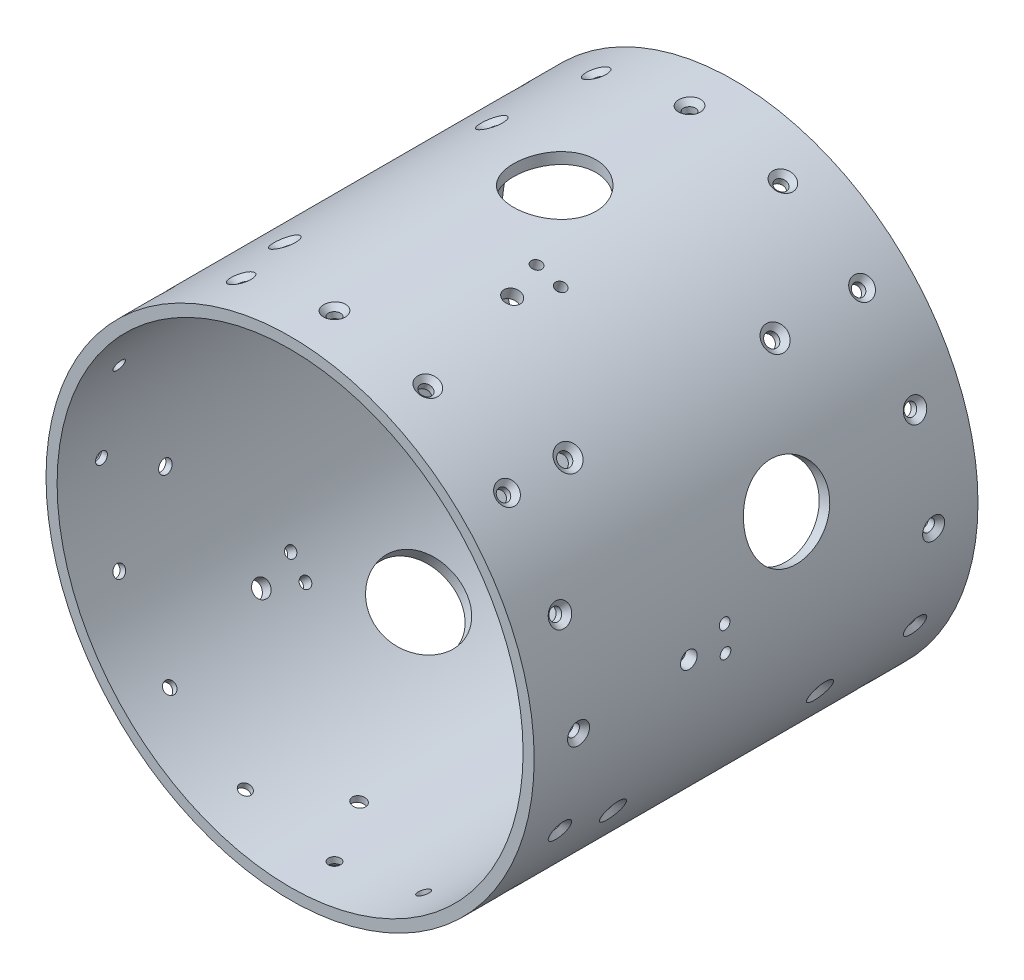
SolidWorks part; units mm, degrees
ref_plane "Front Plane" through (0, 0, 0) normal (0, 0, 1) x (1, 0, 0)
ref_plane "Top Plane" through (0, 0, 0) normal (0, 1, 0) x (1, 0, 0)
ref_plane "Right Plane" through (0, 0, 0) normal (1, 0, 0) x (0, 0, -1)
sketch "Sketch1" plane through (0, 0, 0) normal (0, 0, 1) x (1, 0, 0)
  circle A0 centre (0, 0) radius 66.675
  circle A1 centre (0, 0) radius 69.85
  dimension "D1" = 133.35
  dimension "D2" = 139.7
extrude "Extrude1" add sketch "Sketch1" along normal blind 63.5
ref_plane "Plane2" through (0, 0, 50.8) normal (0, 0, 1) x (1, 0, 0)
sketch "Sketch2" plane through (0, 0, 50.8) normal (0, 0, 1) x (1, 0, 0)
  circle A0 centre (0, 0) radius 69.85 construction
  point P0 (0, -69.85)
ref_plane "Plane3" through (0, -69.85, 50.8) normal (0, -1, 0) x (1, 0, 0)
hole_wizard "CSK for M3 Flat Head Machine Screw1" positions "Sketch4" profile "Sketch3" countersink size "M3" standard "Ansi Metric" end condition through all
sketch "Sketch4" plane through (0, -69.85, 50.8) normal (0, -1, 0) x (1, 0, 0)
  point P1 (0, 0)
sketch "Sketch3" plane through (0, -69.85, 50.8) normal (1, 0, 0) x (0, 0, -1)
  line L0 (0, 0) -> (0, 161.1134)
  line L1 (0, 161.1134) -> (1.7, 161.1134)
  line L2 (1.7, 161.1134) -> (1.7, 1.45)
  line L3 (1.7, 1.45) -> (3.15, 0)
  line L5 (3.15, 0) -> (0, 0)
  line L6 (-1.7, 1.45) -> (-3.15, 0) construction
  line L11 (0, -6.35) -> (0, 107.95) construction
  dimension "Thru Hole Dia." = 3.4
  dimension "Thru Hole Depth" = 161.1134
  dimension "Near C'Sink Dia." = 6.3
  dimension "Near C'Sink Angle" = 90
pattern_circular "CirPattern1" count 16 over 360 about axis through (0, 0, 63.5) along (0, 0, -1) of "CSK for M3 Flat Head Machine Screw1"
mirror "Mirror1" about plane through (0, 0, 0) normal (0, 0, 1) of "CSK for M3 Flat Head Machine Screw1", "CirPattern1", "Extrude1"
sketch "Sketch6" plane through (0, -69.85, 50.8) normal (0, -1, 0) x (1, 0, 0)
  line L0 (0, 12.7) -> (0, -139.319) construction
  line L1 (66.675, 12.7) -> (-66.675, 12.7) construction
  line L2 (0, 12.7) -> (0, -114.3) construction
  line L3 (0, 12.7) -> (0, -37.719) construction
  line L4 (0, 12.7) -> (0, -393.319) construction
  dimension "D1" = 101.6
  dimension "D2" = 50.419
  dimension "D3" = 355.6
ref_plane "Plane4" through (0, 0, 0) normal (-0.7071, -0.7071, 0) x (0.7071, -0.7071, 0)
sketch "Sketch15" plane through (0, 0, -63.5) normal (0, 0, -1) x (-1, 0, 0)
  line L0 (0, 0) -> (0, 69.85) construction
  line L1 (0, 69.85) -> (0, 0) construction
  line L2 (0, 0) -> (-15.7722, 68.046) construction
  line L3 (0, 0) -> (-19.2571, 67.143) construction
  line L4 (0, 0) -> (-22.6931, 66.0609) construction
  line L5 (0, 0) -> (-49.3914, 49.3914) construction
  circle A0 centre (0, 0) radius 69.85 construction
  dimension "D1" = 0
  dimension "D2" = 3.6
  dimension "D3" = 15.875
  dimension "D4" = 7.2
  dimension "D5" = 45
  dimension "D6" = 13.05
  dimension "D7" = 2.953
  dimension "D8" = 2.955
  dimension "D9" = 18.959
  dimension "D10" = 16.003
ref_plane "Plane6" through (0, 69.85, -63.5) normal (0, 1, 0) x (-1, 0, 0)
ref_plane "Plane7" through (19.2571, 67.143, -63.5) normal (0.2757, 0.9612, 0) x (0, 0, 1)
ref_plane "Plane8" through (15.7722, 68.046, -63.5) normal (0.2258, 0.9742, 0) x (-0.9742, 0.2258, 0)
ref_plane "Plane9" through (22.6931, 66.0609, -63.5) normal (0.3249, 0.9458, 0) x (-0.9458, 0.3249, 0)
sketch "Sketch16" plane through (0, 69.85, -63.5) normal (0, 1, 0) x (-1, 0, 0)
  line L0 (0, 51.2766) -> (0, 0) construction
  line L1 (69.85, 127) -> (-69.85, 127) construction
  line L2 (-69.85, 0) -> (69.85, 0) construction
  circle A0 centre (0, 51.2766) radius 11.8
  dimension "D1" = 23.6
  dimension "D2" = 75.7234
  dimension "D3" = 51.2766
extrude "Cut-Extrude1" cut sketch "Sketch16" against normal blind 7.62
sketch "Sketch17" plane through (19.2571, 67.143, -63.5) normal (0.2757, 0.9612, 0) x (0, 0, 1)
  line L0 (0, 0) -> (82.6966, 0) construction
  dimension "D1" = 31.42
sketch "Sketch18" plane through (15.7722, 68.046, -63.5) normal (0.2258, 0.9742, 0) x (-0.9742, 0.2258, 0)
  line L0 (0, 0) -> (0, 72.2466) construction
  dimension "D1" = 10.45
  dimension "D2" = 72.2466
sketch "Sketch27" plane through (22.6931, 66.0609, -63.5) normal (0.3249, 0.9458, 0) x (-0.9458, 0.3249, 0)
  line L0 (0, 0) -> (0, 72.2466) construction
  line L1 (7.1904, 0) -> (7.1904, 72.2466) construction
hole_wizard "#31 (0.12) Diameter Hole1" positions "Sketch22" profile "Sketch23" hole size "#31" standard "ANSI Inch"
sketch "Sketch22" plane through (15.7722, 68.046, -63.5) normal (0.2258, 0.9742, 0) x (-0.9742, 0.2258, 0)
  point P1 (0, 72.2466)
sketch "Sketch23" plane through (15.7722, 68.046, 8.7466) normal (0, 0, 1) x (-0.9742, 0.2258, 0)
  line L0 (0, 0) -> (0, 12.5997)
  line L1 (0, 12.5997) -> (1.524, 11.684)
  line L2 (1.524, 11.684) -> (1.524, 0)
  line L5 (1.524, 0) -> (0, 0)
  line L10 (0, 12.5997) -> (-1.524, 11.684) construction
  line L11 (0, -6.35) -> (0, 107.95) construction
  dimension "Hole Dia." = 3.048
  dimension "Hole Depth" = 11.684
  dimension "Drill Angle" = 118
hole_wizard "3/16 (0.1875) Diameter Hole1" positions "Sketch25" profile "Sketch26" hole size "3/16" standard "ANSI Inch"
sketch "Sketch25" plane through (19.2571, 67.143, -63.5) normal (0.2757, 0.9612, 0) x (0, 0, 1)
  point P1 (82.6966, 0)
sketch "Sketch26" plane through (19.2571, 67.143, 19.1966) normal (0, 0, 1) x (-0.9612, 0.2757, 0)
  line L0 (0, 0) -> (0, 13.1148)
  line L1 (0, 13.1148) -> (2.3812, 11.684)
  line L2 (2.3812, 11.684) -> (2.3812, 0)
  line L5 (2.3812, 0) -> (0, 0)
  line L10 (0, 13.1148) -> (-2.3813, 11.684) construction
  line L11 (0, -6.35) -> (0, 107.95) construction
  dimension "Hole Dia." = 4.7625
  dimension "Hole Depth" = 11.684
  dimension "Drill Angle" = 118
hole_wizard "#31 (0.12) Diameter Hole3" positions "Sketch29" profile "Sketch28" hole size "#31" standard "ANSI Inch"
sketch "Sketch29" plane through (22.6931, 66.0609, -63.5) normal (0.3249, 0.9458, 0) x (-0.9458, 0.3249, 0)
  point P0 (0, 72.2466)
sketch "Sketch28" plane through (22.6931, 66.0609, 8.7466) normal (0, 0, 1) x (-0.9458, 0.3249, 0)
  line L0 (0, 0) -> (0, 12.5997)
  line L1 (0, 12.5997) -> (1.524, 11.684)
  line L2 (1.524, 11.684) -> (1.524, 0)
  line L5 (1.524, 0) -> (0, 0)
  line L10 (0, 12.5997) -> (-1.524, 11.684) construction
  line L11 (0, -6.35) -> (0, 107.95) construction
  dimension "Hole Dia." = 3.048
  dimension "Hole Depth" = 11.684
  dimension "Drill Angle" = 118
ref_plane "Plane10" through (49.3914, 49.3914, -63.5) normal (0.7071, 0.7071, 0) x (-0.7071, 0.7071, 0)
sketch "Sketch30" plane through (49.3914, 49.3914, -63.5) normal (0.7071, 0.7071, 0) x (-0.7071, 0.7071, 0)
  line L0 (0, 0) -> (0, 37.5945) construction
  line L1 (0, 37.5945) -> (0, 96.8375) construction
  line L3 (66.675, 127) -> (-66.675, 127) construction
  dimension "D1" = 30.1625
  dimension "D2" = 59.243
  dimension "D3" = 37.5945
  dimension "D4" = 96.8375
hole_wizard "CSK for #6 Flat Head Machine Screw (100)1" positions "Sketch34" profile "Sketch35" countersink size "#6" standard "ANSI Inch"
sketch "Sketch34" plane through (49.3914, 49.3914, -63.5) normal (0.7071, 0.7071, 0) x (-0.7071, 0.7071, 0)
  point P0 (0, 96.8375)
  point P3 (0, 37.5945)
sketch "Sketch35" plane through (49.3914, 49.3914, 33.3375) normal (0, 0, 1) x (-0.7071, 0.7071, 0)
  line L0 (0, 0) -> (0, 16.3808)
  line L1 (0, 16.3808) -> (1.8986, 15.24)
  line L2 (1.8986, 15.24) -> (1.8986, 1.38)
  line L3 (1.8986, 1.38) -> (3.5433, 0)
  line L5 (3.5433, 0) -> (0, 0)
  line L6 (-1.8986, 1.38) -> (-3.5433, 0) construction
  line L10 (0, 16.3808) -> (-1.8987, 15.24) construction
  line L11 (0, -6.35) -> (0, 107.95) construction
  dimension "Hole Dia." = 3.7973
  dimension "Hole Depth" = 15.24
  dimension "Near C'Sink Dia." = 7.0866
  dimension "Near C'Sink Angle" = 100
  dimension "Drill Angle" = 118
pattern_circular "CirPattern2" count 5 over 360 about axis through (0, 0, 63.5) along (0, 0, -1) of "Cut-Extrude1", "#31 (0.12) Diameter Hole1", "3/16 (0.1875) Diameter Hole1", "#31 (0.12) Diameter Hole3", "CSK for #6 Flat Head Machine Screw (100)1"
sketch "Sketch36" plane through (0, 0, -63.5) normal (0, 0, -1) x (-1, 0, 0)
  line L0 (-66.4313, 21.5848) -> (0, 0) construction
  line L1 (-62.4107, 20.2785) -> (-65.4765, 21.2746) construction
  line L2 (0, 0) -> (-49.3914, 49.3914) construction
  line L3 (0, 0) -> (-22.6931, 66.0609) construction
  circle A0 centre (0, 0) radius 69.85 construction
  dimension "D1" = 27
  dimension "D2" = 53.041
